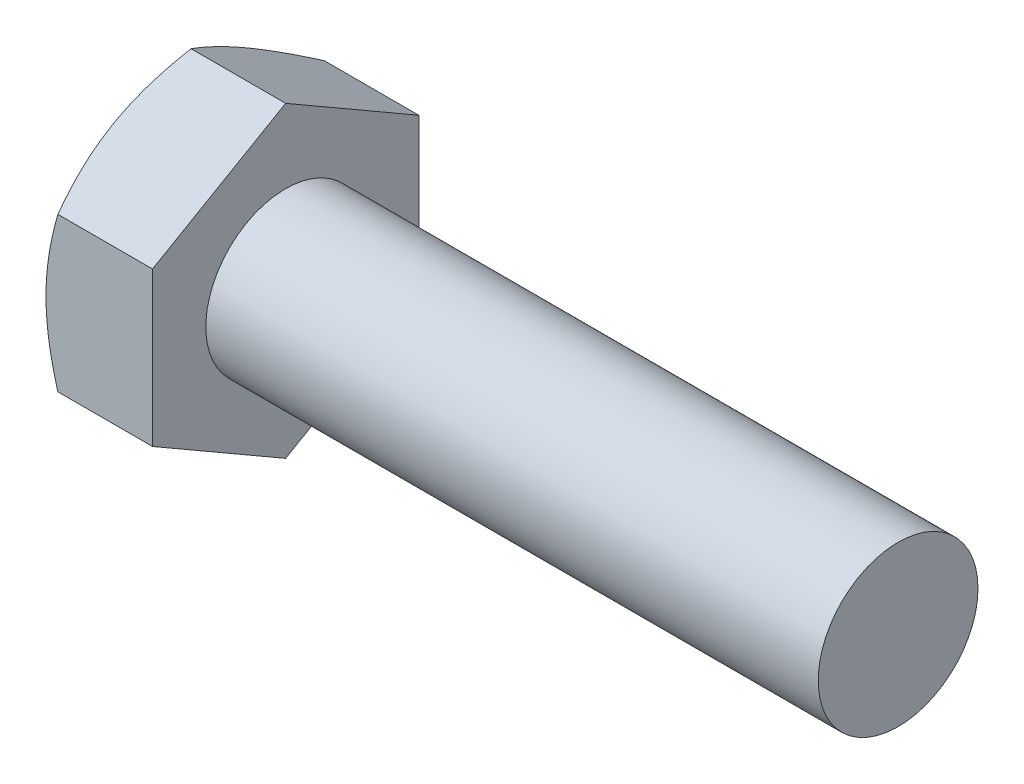
SolidWorks part; units mm, degrees
material "Alloy Steel"
ref_plane "Front Plane" through (0, 0, 0) normal (0, 0, 1) x (1, 0, 0)
ref_plane "Top Plane" through (0, 0, 0) normal (0, 1, 0) x (1, 0, 0)
ref_plane "Right Plane" through (0, 0, 0) normal (1, 0, 0) x (0, 0, -1)
sketch "Sketch1" plane through (0, 0, 0) normal (0, 0, 1) x (1, 0, 0)
  line L0 (-17, 0) -> (17, 0) construction
  line L1 (-13, 5) -> (-13, -5) construction
  line L2 (-17, 5) -> (-17, -5) construction
  line L3 (17, 3) -> (17, -3) construction
  point P8 (13.5, -3)
  dimension "Thread Dia" = 6
  dimension "Hex" = 10
  dimension "Head Ht" = 4
  dimension "Length" = 30
  dimension "D1" = 3.5
ref_plane "Plane2" through (17, 0, 0) normal (1, 0, 0) x (0, 0, -1)
sketch "Sketch2" plane through (17, 0, 0) normal (1, 0, 0) x (0, 0, -1)
  circle A0 centre (0, 0) radius 3
extrude "Boss-Extrude1" add sketch "Sketch2" against normal up to vertex (30 mm away) up to point (-13, -5, 0)
sketch "Sketch4" plane through (17, 0, 0) normal (1, 0, 0) x (0, 0, -1)
  circle A1 centre (0, 0) radius 3
  circle A2 centre (0, 0) radius 3
  dimension "D1" = 0
curve "Helix/Spiral1" pitch 1 height 31 turns 31 parameters "Pitch"=1
chamfer "Chamfer1" distance 0.75 angle 45 1 edges at (17, 0, -3)
sketch "Sketch5" plane through (0, 0, 0) normal (0, 0, 1) x (1, 0, 0)
  line L0 (17, 3) -> (17.375, 2.3505)
  line L1 (17.375, 2.3505) -> (17.5, 2.3505)
  line L2 (17.5, 2.3505) -> (17.875, 3)
  line L3 (17, 3) -> (17.875, 3)
  line L4 (17.4375, 2.3505) -> (17.4375, 3) construction
  line L5 (17.1875, 2.6752) -> (17.6875, 2.6752) construction
  line L6 (17, -3) -> (17, 3) construction
  dimension "D1" = 60
  dimension "D2" = 0.125
  dimension "D3" = 0.5
sweep "Cut-Sweep1" [suppressed] cut profiles "Sketch5" path "Helix/Spiral1"
sketch "Sketch3" plane through (-13, 0, 0) normal (-1, 0, 0) x (0, 0, 1)
  line L0 (0, 5) -> (0, -5) construction
  line L1 (-5, -2.8868) -> (0, -5.7735)
  line L2 (0, -5.7735) -> (5, -2.8868)
  line L3 (5, -2.8868) -> (5, 2.8868)
  line L4 (5, 2.8868) -> (0, 5.7735)
  line L5 (0, 5.7735) -> (-5, 2.8868)
  line L6 (-5, 2.8868) -> (-5, -2.8868)
  circle A0 centre (0, 0) radius 5 construction
extrude "Boss-Extrude2" add sketch "Sketch3" along normal up to vertex (4 mm away) up to point (-17, -5, 0)
sketch "Sketch6" plane through (-17, 0, 0) normal (-1, 0, 0) x (0, 0, 1)
  circle A0 centre (0, 0) radius 5 construction
  circle A1 centre (0, 0) radius 5
extrude "Cut-Extrude1" cut sketch "Sketch6" against normal through all draft 60 flip side to cut
sketch "Sketch7" plane through (-17, 0, 0) normal (-1, 0, 0) x (0, 0, 1)
  line L0 (0, 0) -> (0, 5) construction
  line L2 (0, 5) -> (0, -5) construction
  line L3 (-4.3301, 2.5) -> (4.3301, 2.5) construction
  circle A1 centre (0, 0) radius 5 construction
  text T0 "10.9" font "Arial" height in points 6
  point P8 (0, 2.5)
extrude "Cut-Extrude2" cut sketch "Sketch7" against normal blind 0.25
sketch "Sketch9" plane through (0, 0, 0) normal (0, 0, 1) x (1, 0, 0)
  line L0 (-13, 3) -> (-13, 0)
  line L1 (-13, 0) -> (2, 0)
  line L2 (2, 0) -> (-1, 3)
  line L3 (-1, 3) -> (-13, 3)
  line L4 (-17, 0) -> (17, 0) construction
  line L5 (-13, 5) -> (-13, -5) construction
  line L6 (17, 3) -> (17, -3) construction
  dimension "D1" = 45
  dimension "MinThreadLg" = 18
revolve "Revolve1" add sketch "Sketch9" angle 360 about L1
sketch "Sketch10" plane through (17, 0, 0) normal (1, 0, 0) x (0, 0, -1)
  circle A0 centre (0, 0) radius 3.9032
extrude "Cut-Extrude3" cut sketch "Sketch10" against normal blind 7
equation "\"D2@Sketch5\" = \"Pitch@Helix/Spiral1\"*.125"
equation "\"D3@Sketch5\" = \"Pitch@Helix/Spiral1\"*.50"
equation "\"D3@Helix/Spiral1\" = \"Length@Sketch1\"+\"Pitch@Helix/Spiral1\""
equation "\"D1@Chamfer1\" = \"Pitch@Helix/Spiral1\"*.750"
equation "\"D1@Sketch1\" = \"Pitch@Helix/Spiral1\"*3.50"
